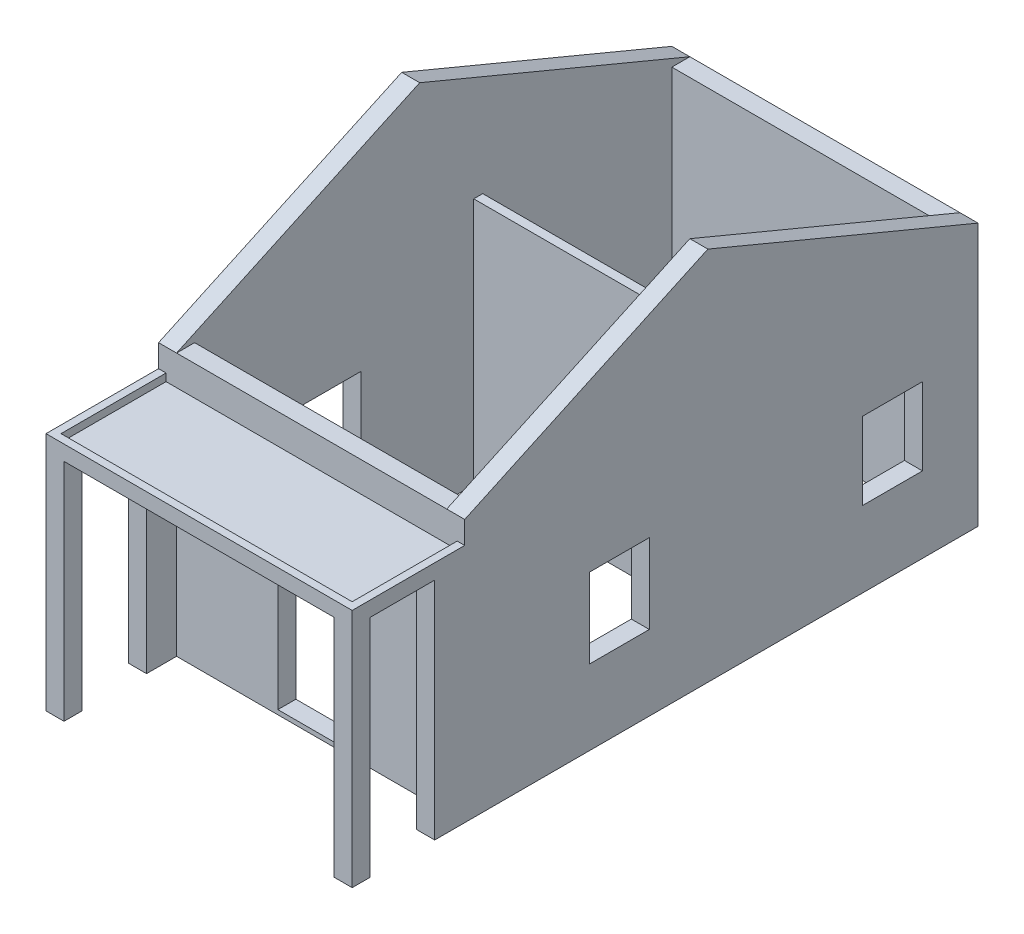
SolidWorks part; units mm, degrees
material "屋面瓦"
ref_plane "前视基准面" through (0, 0, 0) normal (0, 0, 1) x (1, 0, 0)
ref_plane "上视基准面" through (0, 0, 0) normal (0, 1, 0) x (1, 0, 0)
ref_plane "右视基准面" through (0, 0, 0) normal (1, 0, 0) x (0, 0, -1)
sketch "草图1" plane through (0, 0, 0) normal (0, 1, 0) x (1, 0, 0)
  line L1 (0, 0) -> (-3600, 0)
  line L2 (0, 0) -> (0, 6360)
  line L3 (0, 6360) -> (-3600, 6360)
  line L4 (-3600, 0) -> (-3600, 6360)
  point P4 (-1800, 0)
  dimension "D1" = 6360
  dimension "D2" = 3600
extrude "墙" add sketch "草图1" along normal blind 3500 thin thin type one direction wall 240
ref_plane "中间面-宽向" through (-1800, 0, 0) normal (1, 0, 0) x (0, 0, -1)
sketch "草图14" plane through (240, 0, 0) normal (1, 0, 0) x (0, 0, -1)
  line L0 (-240, 3500) -> (3000, 5000)
  line L1 (3000, 5000) -> (6600, 3500)
  line L2 (-240, 0) -> (6600, 0) construction
  line L3 (-240, 3500) -> (6600, 3500)
  dimension "D1" = 5000
  dimension "D2" = 3600
extrude "三角墙" add sketch "草图14" against normal blind 240
mirror "镜向1" about plane through (-1800, 0, 0) normal (1, 0, 0) of "三角墙"
sketch "草图6" plane through (0, 0, 0) normal (0, 1, 0) x (1, 0, 0)
  line L0 (-3600, 3840) -> (0, 3840)
  line L4 (-3600, 6360) -> (-3600, 6600) construction
  line L5 (0, 0) -> (0, -240) construction
  line L6 (0, 6360) -> (-3600, 6360) construction
  dimension "D1" = 2520
extrude "房墙" add sketch "草图6" along normal blind 3300 thin thin type one direction wall 120
sketch "草图12" plane through (0, 0, 0) normal (0, 1, 0) x (1, 0, 0)
  line L0 (-1200, 3960) -> (-1200, 3840) construction
  line L1 (0, 3840) -> (-1440, 3840)
  line L2 (0, 3840) -> (0, 3960)
  line L3 (0, 3960) -> (-1440, 3960)
  line L4 (-1440, 3840) -> (-1440, 3960)
  line L5 (-200, 3960) -> (-200, 3840) construction
  dimension "D1" = 200
  dimension "D2" = 120
  dimension "D3" = 240
  dimension "D4" = 1000
extrude "房门框" add sketch "草图12" along normal blind 2520
sketch "草图10" plane through (0, 0, -3720) normal (0, 0, 1) x (1, 0, 0)
  line L0 (-3600, 0) -> (0, 0) construction
  line L1 (-1200, 2050) -> (-200, 2050)
  line L2 (-1200, 2050) -> (-1200, 0)
  line L3 (-1200, 0) -> (-200, 0)
  line L4 (-200, 2050) -> (-200, 0)
  dimension "D1" = 2050
extrude "房门" cut sketch "草图10" against normal up to next
sketch "草图4" plane through (0, 0, -11000) normal (-1, 0, 0) x (0, 0, 1)
  line L0 (11240, 0) -> (4400, 0) construction
  line L1 (5140, 2040) -> (5940, 2040)
  line L2 (5140, 2040) -> (5140, 1010)
  line L3 (5140, 1010) -> (5940, 1010)
  line L4 (5940, 2040) -> (5940, 1010)
  line L6 (4640, 3500) -> (4640, 0) construction
  dimension "D1" = 1030
  dimension "D2" = 800
  dimension "D3" = 1010
  dimension "D4" = 500
extrude "房窗" cut sketch "草图4" against normal through all
sketch "草图13" plane through (0, 0, 240) normal (0, 0, 1) x (1, 0, 0)
  line L0 (0, 3500) -> (0, 0) construction
  line L1 (-2250, 2580) -> (-1250, 2580)
  line L2 (-2250, 2580) -> (-2250, 60)
  line L3 (-2250, 60) -> (-1250, 60)
  line L4 (-1250, 2580) -> (-1250, 60)
  line L5 (-3840, 0) -> (240, 0) construction
  dimension "D1" = 2520
  dimension "D2" = 60
  dimension "D3" = 1000
  dimension "D4" = 1250
extrude "大门" cut sketch "草图13" against normal up to next
sketch "草图15" plane through (240, 0, 0) normal (1, 0, 0) x (0, 0, -1)
  line L0 (-240, 3500) -> (-240, 0) construction
  line L1 (-240, 3100) -> (-1740, 3100)
  line L2 (-240, 3100) -> (-240, 3000)
  line L3 (-240, 3000) -> (-1740, 3000)
  line L4 (-1740, 3100) -> (-1740, 3000)
  line L5 (-240, 0) -> (6600, 0) construction
  dimension "D1" = 100
  dimension "D2" = 3000
  dimension "D3" = 1500
extrude "凸台" add sketch "草图15" against normal up to surface (4080 mm away) up to face at (-3840, 2400, -3144)
sketch "草图16" plane through (0, 3100, 0) normal (0, 1, 0) x (1, 0, 0)
  line L1 (240, -240) -> (0, -240)
  line L2 (240, -240) -> (240, -640)
  line L3 (240, -640) -> (0, -640)
  line L4 (0, -240) -> (0, -640)
  line L5 (240, -1740) -> (0, -1740)
  line L6 (240, -1740) -> (240, -1500)
  line L7 (240, -1500) -> (0, -1500)
  line L8 (0, -1740) -> (0, -1500)
  dimension "D1" = 400
  dimension "D2" = 240
  dimension "D3" = 240
extrude "立柱" add sketch "草图16" against normal up to surface (3100 mm away) up to face at (-1434.2857, 0, -3651.4286)
mirror "镜向-立柱" about plane through (-1800, 0, 0) normal (1, 0, 0) of "立柱"
sketch "草图17" plane through (0, 3100, 0) normal (0, 1, 0) x (1, 0, 0)
  line L0 (-3840, -1740) -> (-3840, -240) construction
  line L1 (240, -240) -> (240, -1740) construction
  line L2 (-3840, -1740) -> (-3840, -240)
  line L3 (240, -240) -> (240, -1740)
  line L4 (-3840, -1740) -> (240, -1740) construction
  line L5 (-3840, -1740) -> (240, -1740)
extrude "凸边" add sketch "草图17" along normal blind 100 thin thin type one direction wall 100
sketch "草图18" plane through (240, 0, 0) normal (1, 0, 0) x (0, 0, -1)
  line L0 (-640, 0) -> (6600, 0) construction
  line L1 (1420, 2060) -> (2220, 2060)
  line L2 (1420, 2060) -> (1420, 1000)
  line L3 (1420, 1000) -> (2220, 1000)
  line L4 (2220, 2060) -> (2220, 1000)
  line L5 (3720, 3300) -> (3720, 0) construction
  dimension "D1" = 1060
  dimension "D2" = 800
  dimension "D3" = 1000
  dimension "D4" = 1500
extrude "厅窗" cut sketch "草图18" against normal through all
